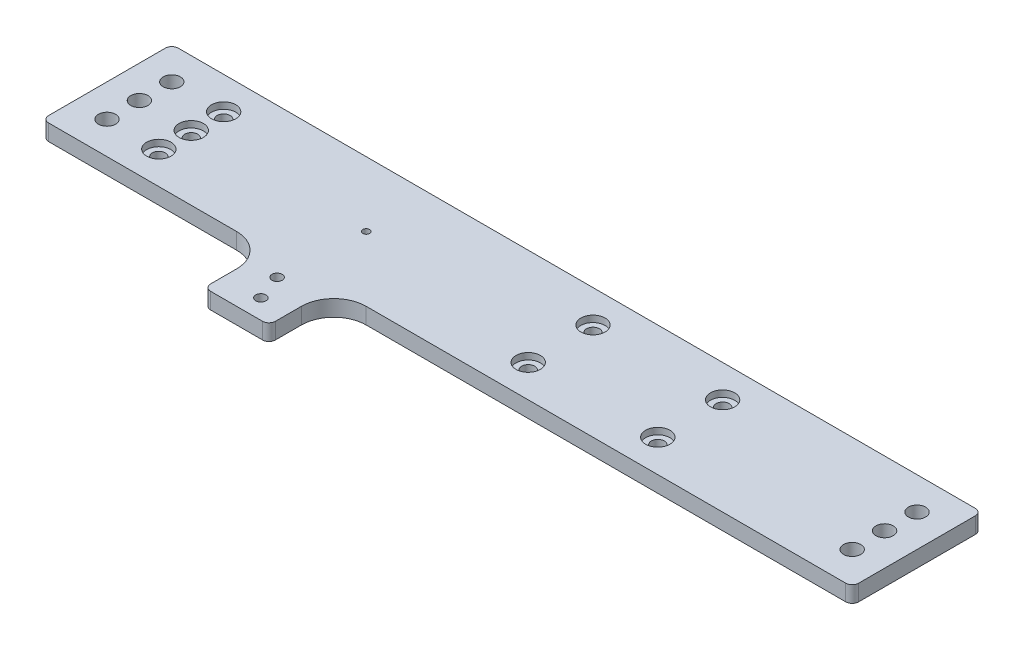
SolidWorks part; units mm, degrees
material "6061-T6 (SS)"
ref_plane "Front" through (0, 0, 0) normal (0, 0, 1) x (1, 0, 0)
ref_plane "Top" through (0, 0, 0) normal (0, 1, 0) x (1, 0, 0)
ref_plane "Right" through (0, 0, 0) normal (1, 0, 0) x (0, 0, -1)
sketch "Sketch1" plane through (0, 0, 0) normal (0, 1, 0) x (1, 0, 0)
  line L1 (-158.75, -25.4) -> (158.75, -25.4)
  line L2 (-158.75, -25.4) -> (-158.75, 25.4)
  line L3 (-158.75, 25.4) -> (158.75, 25.4)
  line L4 (158.75, -25.4) -> (158.75, 25.4)
  line L5 (-158.75, -25.4) -> (158.75, 25.4) construction
  line L6 (-158.75, 25.4) -> (158.75, -25.4) construction
  point P0 (0, 0)
  dimension "D1" = 50.8
  dimension "D2" = 317.5
extrude "Boss-Extrude1" add sketch "Sketch1" along normal blind 6.35
hole_wizard "CBORE for #10 Socket Head Cap Screw1" positions "Sketch2" profile "Sketch4" counterbore size "#10" standard "ANSI Inch" end condition through all
sketch "Sketch2" plane through (0, 6.35, 0) normal (0, 1, 0) x (1, 0, 0)
  line L2 (158.75, 25.4) -> (-158.75, 25.4) construction
  line L6 (-158.75, -25.4) -> (158.75, -25.4) construction
  line L8 (-158.75, 25.4) -> (-158.75, -25.4) construction
  line L12 (158.75, -25.4) -> (158.75, 25.4) construction
  line L15 (19.05, 12.7) -> (19.05, 25.4) construction
  line L17 (19.05, -12.7) -> (19.05, -25.4) construction
  line L18 (-125.73, -25.4) -> (-125.73, -12.7) construction
  line L20 (-125.73, 0) -> (-125.73, 12.7) construction
  line L21 (-125.73, 12.7) -> (-125.73, 25.4) construction
  line L22 (-125.73, 0) -> (-125.73, -12.7) construction
  point P64 (19.05, 12.7)
  point P66 (69.85, 12.7)
  point P68 (19.05, -12.7)
  point P70 (69.85, -12.7)
  point P92 (-125.73, 12.7)
  point P94 (-125.73, 0)
  point P102 (-125.73, -12.7)
  dimension "D2" = 50.8
  dimension "D3" = 25.4
  dimension "D4" = 88.9
  dimension "D5" = 33.02
sketch "Sketch4" plane through (-125.73, 6.35, 12.7) normal (1, 0, 0) x (0, 0, 1)
  line L0 (0, 0) -> (0, 6.35)
  line L1 (0, 6.35) -> (2.5527, 6.35)
  line L3 (2.5527, 6.35) -> (2.5527, 2.54)
  line L4 (2.5527, 2.54) -> (4.7625, 2.54)
  line L5 (4.7625, 2.54) -> (4.7625, 0)
  line L7 (4.7625, 0) -> (0, 0)
  line L11 (0, -6.35) -> (0, 107.95) construction
  dimension "Thru Hole Dia." = 5.1054
  dimension "Thru Hole Depth" = 6.35
  dimension "C'Bore Dia." = 9.525
  dimension "C'Bore Depth" = 2.54
sketch "Sketch7" plane through (0, 0, 0) normal (0, -1, 0) x (1, 0, 0)
  line L0 (-146.05, 25.4) -> (-146.05, 12.7) construction
  line L1 (-158.75, 25.4) -> (158.75, 25.4) construction
  line L2 (-146.05, 12.7) -> (-146.05, 0) construction
  line L3 (-146.05, 0) -> (-146.05, -12.7) construction
  line L4 (-146.05, -12.7) -> (-146.05, -25.4) construction
  line L5 (158.75, -25.4) -> (-158.75, -25.4) construction
  line L7 (-158.75, -25.4) -> (-158.75, 25.4) construction
  line L8 (146.05, 25.4) -> (146.05, 12.7) construction
  line L9 (146.05, 12.7) -> (146.05, 0) construction
  line L10 (146.05, 0) -> (146.05, -12.7) construction
  line L11 (146.05, -12.7) -> (146.05, -25.4) construction
  line L13 (158.75, 25.4) -> (158.75, -25.4) construction
  point P0 (-146.05, 12.7)
  point P2 (-146.05, 0)
  point P4 (-146.05, -12.7)
  point P6 (146.05, 12.7)
  point P8 (146.05, 0)
  point P10 (146.05, -12.7)
  dimension "D1" = 12.7
  dimension "D2" = 12.7
hole_wizard "1/4 Clearance Hole2" positions "Sketch7" profile "Sketch6" hole size "1/4" standard "ANSI Inch" end condition through all
sketch "Sketch6" plane through (-146.05, 0, 12.7) normal (1, 0, 0) x (0, 0, -1)
  line L0 (0, 0) -> (0, 6.35)
  line L1 (0, 6.35) -> (3.3782, 6.35)
  line L2 (3.3782, 6.35) -> (3.3782, 0)
  line L5 (3.3782, 0) -> (0, 0)
  line L11 (0, -6.35) -> (0, 107.95) construction
  dimension "Thru Hole Dia." = 6.7564
  dimension "Thru Hole Depth" = 6.35
sketch "Sketch10" plane through (0, 0, 0) normal (0, -1, 0) x (-1, 0, 0)
  line L0 (158.75, 25.4) -> (158.75, -25.4) construction
  point P0 (57.15, 0)
  dimension "D1" = 101.6
hole_wizard "#6-32 Tapped Hole1" positions "Sketch10" profile "Sketch9" tap size "#6-32" standard "ANSI Inch" end condition through all
sketch "Sketch9" plane through (-57.15, 0, 0) normal (1, 0, 0) x (0, 0, -1)
  line L0 (0, 0) -> (0, 6.35)
  line L1 (0, 6.35) -> (1.3525, 6.35)
  line L2 (1.3525, 6.35) -> (1.3525, 0)
  line L5 (1.3525, 0) -> (0, 0)
  line L11 (0, -6.35) -> (0, 107.95) construction
  dimension "Thru Tap Drill Dia." = 2.7051
  dimension "Thru Tap Drill Depth" = 6.35
cosmetic thread "Hole Thread1" parameters "D2"=3.5052
sketch "Sketch11" plane through (0, 0, 0) normal (0, -1, 0) x (1, 0, 0)
  line L0 (158.75, -25.4) -> (-158.75, -25.4) construction
  line L1 (-70.0118, -25.4) -> (-48.1024, -25.4)
  line L2 (-70.0118, -25.4) -> (-70.0118, -45.81)
  line L3 (-70.0118, -45.81) -> (-48.1024, -45.81)
  line L4 (-48.1024, -25.4) -> (-48.1024, -45.81)
extrude "Boss-Extrude2" [suppressed] add sketch "Sketch11" against normal up to surface (6.35 mm away) up to face at (-57.15, 6.35, -1.3526)
sketch "Sketch12" plane through (0, 6.35, 0) normal (0, 1, 0) x (1, 0, 0)
  line L0 (-158.75, -25.4) -> (158.75, -25.4) construction
  line L1 (-69.85, -25.4) -> (-44.45, -25.4)
  line L2 (-69.85, -25.4) -> (-69.85, -50.8)
  line L3 (-69.85, -50.8) -> (-44.45, -50.8)
  line L4 (-44.45, -25.4) -> (-44.45, -50.8)
  line L5 (-158.75, 25.4) -> (-158.75, -25.4) construction
  dimension "D1" = 88.9
  dimension "D2" = 25.4
  dimension "D3" = 25.4
extrude "Boss-Extrude3" add sketch "Sketch12" against normal up to surface (6.35 mm away) up to face at (-57.15, 0, -1.3526)
sketch "Sketch15" plane through (0, 0, 0) normal (0, -1, 0) x (-1, 0, 0)
  point P0 (55.245, -43.18)
  point P3 (59.055, -33.02)
hole_wizard "#10-32 Tapped Hole1" positions "Sketch15" profile "Sketch14" tap size "#10-32" standard "ANSI Inch" end condition through all
sketch "Sketch14" plane through (-55.245, 0, 43.18) normal (1, 0, 0) x (0, 0, -1)
  line L0 (0, 0) -> (0, 6.35)
  line L1 (0, 6.35) -> (2.0193, 6.35)
  line L2 (2.0193, 6.35) -> (2.0193, 0)
  line L5 (2.0193, 0) -> (0, 0)
  line L11 (0, -6.35) -> (0, 107.95) construction
  dimension "Thru Tap Drill Dia." = 4.0386
  dimension "Thru Tap Drill Depth" = 6.35
fillet "Fillet1" radius 12.7 2 edges at (-69.85, 3.175, 25.4) (-44.45, 3.175, 25.4)
fillet "Fillet2" radius 2.54 6 edges at (158.75, 3.175, 25.4) (158.75, 3.175, -25.4) (-158.75, 3.175, -25.4) (-158.75, 3.175, 25.4) (-69.85, 3.175, 50.8) (-44.45, 3.175, 50.8)
